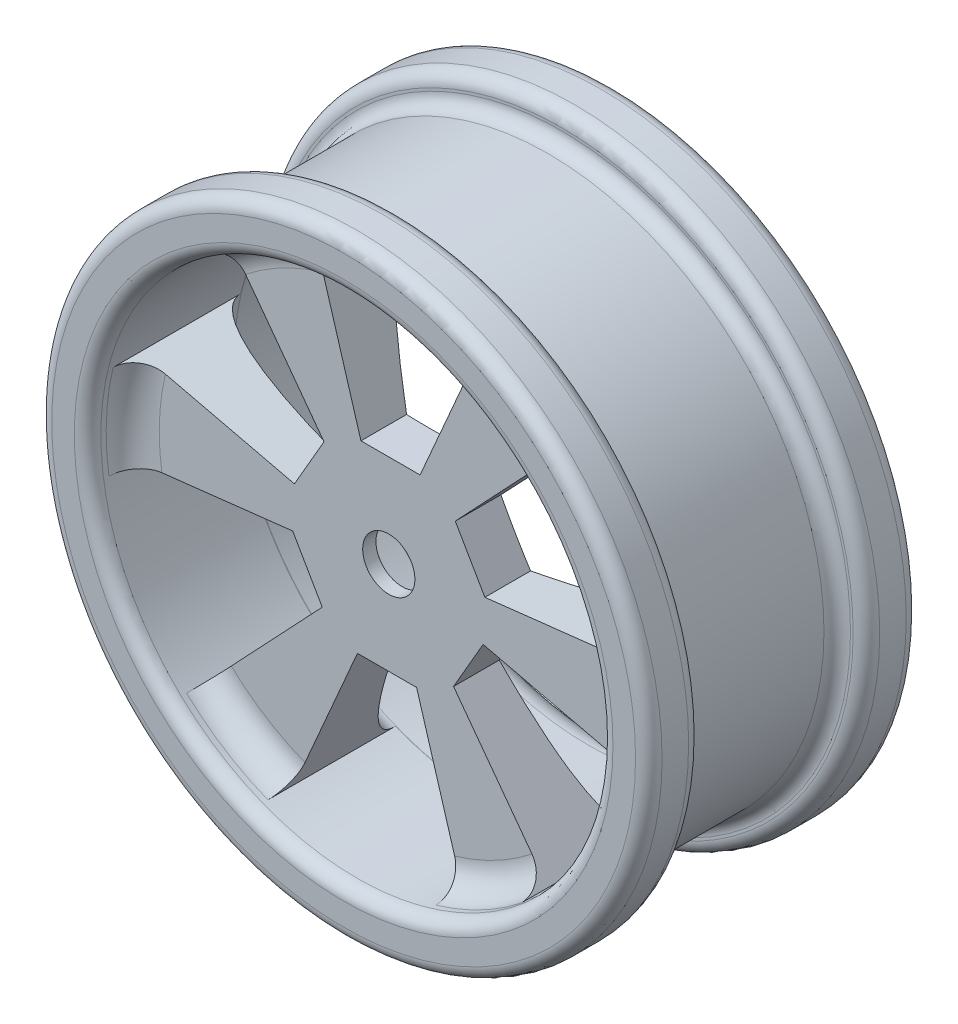
SolidWorks part; units mm, degrees
material "ABS"
ref_plane "Front Plane" through (0, 0, 0) normal (0, 0, 1) x (1, 0, 0)
ref_plane "Top Plane" through (0, 0, 0) normal (0, 1, 0) x (1, 0, 0)
ref_plane "Right Plane" through (0, 0, 0) normal (1, 0, 0) x (0, 0, -1)
sketch "Sketch1" plane through (0, 0, 0) normal (1, 0, 0) x (0, 0, -1)
  line L0 (0, 0) -> (59.5506, 0) construction
  line L1 (0, 0) -> (0, 24.511) construction
  line L2 (0, 24.511) -> (15.24, 24.511) construction
  line L3 (17.78, 27.051) -> (17.78, 27.94)
  line L4 (16.51, 29.21) -> (13.97, 29.21)
  line L5 (12.7, 27.94) -> (12.7, 27.686)
  line L6 (11.43, 26.416) -> (-1.778, 26.416)
  line L7 (-3.048, 27.686) -> (-3.048, 27.94)
  line L8 (-4.318, 29.21) -> (-6.858, 29.21)
  line L9 (-8.128, 27.94) -> (-8.128, 25.781)
  line L10 (-6.858, 24.511) -> (-6.35, 24.511)
  line L11 (-3.81, 21.971) -> (-3.81, 0)
  line L12 (-3.81, 0) -> (0, 0)
  line L13 (5.9013, 24.511) -> (15.24, 24.511)
  arc A0 (-6.35, 24.511) -> (-3.81, 21.971) centre (-6.35, 21.971) cw
  arc A1 (16.51, 29.21) -> (17.78, 27.94) centre (16.51, 27.94) cw
  arc A2 (13.97, 29.21) -> (12.7, 27.94) centre (13.97, 27.94) ccw
  arc A3 (-6.858, 29.21) -> (-8.128, 27.94) centre (-6.858, 27.94) ccw
  arc A4 (-4.318, 29.21) -> (-3.048, 27.94) centre (-4.318, 27.94) cw
  arc A5 (12.7, 27.686) -> (11.43, 26.416) centre (11.43, 27.686) cw
  arc A6 (-3.048, 27.686) -> (-1.778, 26.416) centre (-1.778, 27.686) ccw
  arc A7 (-6.858, 24.511) -> (-8.128, 25.781) centre (-6.858, 25.781) cw
  arc A8 (17.78, 27.051) -> (15.24, 24.511) centre (15.24, 27.051) cw
  spline S0 degree 3 poles (5.9013, 24.511) (1.3034, 24.5738) (0.1122, 6.6307) (0, 0) knots 0 0 0 0 0.942973 0.942973 0.942973 0.942973
  point P22 (12.7, 29.21)
  point P29 (12.7, 26.416)
  point P36 (17.78, 24.511)
  dimension "D8" = 2.54
  dimension "D9" = 1.27
  dimension "D10" = 2.54
  dimension "D11" = 49.022
  dimension "D1" = 58.42
  dimension "D2" = 2.794
  dimension "D4" = 5.08
  dimension "D5" = 3.81
  dimension "D6" = 25.908
  dimension "D7" = 17.78
revolve "Body" add sketch "Sketch1" angle 360 about L0
sketch "Sketch2" plane through (0, 0, 0) normal (0, 0, 1) x (1, 0, 0)
  line L0 (-2.6636, 8.89) -> (2.9969, 8.89)
  line L1 (3.497, -6.4447) -> (7.3298, -0.1939)
  line L2 (7.3298, -0.1939) -> (3.8328, 6.2508)
  line L3 (3.8328, 6.2508) -> (-3.497, 6.4447)
  line L4 (-3.497, 6.4447) -> (-7.3298, 0.1939)
  line L5 (-7.3298, 0.1939) -> (-3.8328, -6.2508)
  line L6 (-3.8328, -6.2508) -> (3.497, -6.4447)
  line L7 (2.9969, 8.89) -> (9.0315, 22.7864)
  line L8 (-2.6636, 8.89) -> (-7.035, 23.4797)
  circle A0 centre (0, 0) radius 6.35 construction
  circle A1 centre (0, 0) radius 24.511 construction
  arc A2 (-7.035, 23.4797) -> (9.0315, 22.7864) centre (0, 0) cw
  circle A3 centre (0, 0) radius 2.5
  circle A4 centre (0, 0) radius 7.3323 construction
  dimension "D1" = 5
  dimension "D2" = 12.7
  dimension "D3" = 8.89
extrude "Nut" cut sketch "Sketch2" against normal blind 8.89 and the other way blind 2.54 contours L2 L3 L4 L5 L6 L1
extrude "Spokes" cut sketch "Sketch2<3>" against normal through all both and the other way through all contours L7 A2 L8 L0
sketch "Sketch2<3>" plane through (0, 0, 0) normal (0, 0, 1) x (1, 0, 0) same geometry as "Sketch2"
pattern_circular "CirPattern1" count 6 over 360 about axis through (0, 0, 0) along (0, 0, 1) of "Spokes"
extrude "Axle" cut sketch "Sketch2<4>" along normal through all both and the other way through all contours A3
sketch "Sketch2<4>" plane through (0, 0, 0) normal (0, 0, 1) x (1, 0, 0) same geometry as "Sketch2"
